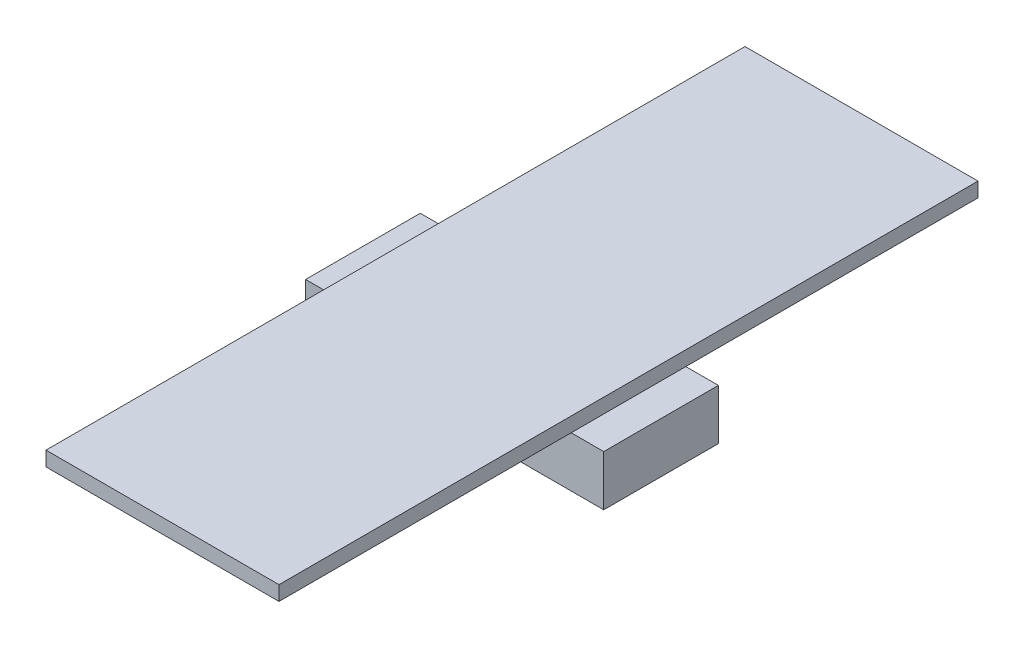
SolidWorks part; units mm, degrees
ref_plane "Front Plane" through (0, 0, 0) normal (0, 0, 1) x (1, 0, 0)
ref_plane "Top Plane" through (0, 0, 0) normal (0, 1, 0) x (1, 0, 0)
ref_plane "Right Plane" through (0, 0, 0) normal (1, 0, 0) x (0, 0, -1)
sketch "Sketch1" plane through (0, 0, 0) normal (0, 1, 0) x (1, 0, 0)
  line L1 (-65, -25) -> (65, -25)
  line L2 (-65, -25) -> (-65, 25)
  line L3 (-65, 25) -> (65, 25)
  line L4 (65, -25) -> (65, 25)
  line L5 (0, 25) -> (0, -25) construction
  line L6 (-65, 0) -> (65, 0) construction
  point P0 (0, 0)
  dimension "D1" = 130
  dimension "D2" = 50
extrude "Boss-Extrude1" add sketch "Sketch1" along normal blind 22
sketch "Sketch2" plane through (0, 0, 25) normal (0, 0, 1) x (1, 0, 0)
  ellipse E0 centre (0, 11) end of major axis (15.4617, 11) minor radius 5.8847
extrude "Cut-Extrude1" cut sketch "Sketch2" against normal through all
sketch "Sketch3" plane through (0, 22, 0) normal (0, 1, 0) x (1, 0, 0)
  line L1 (-50.8, -152.4) -> (50.8, -152.4)
  line L2 (-50.8, -152.4) -> (-50.8, 152.4)
  line L3 (-50.8, 152.4) -> (50.8, 152.4)
  line L4 (50.8, -152.4) -> (50.8, 152.4)
  line L5 (0, 152.4) -> (0, -152.4) construction
  line L6 (-50.8, 0) -> (50.8, 0) construction
  point P0 (0, 0)
  dimension "D1" = 101.6
  dimension "D2" = 304.8
extrude "Boss-Extrude2" add sketch "Sketch3" along normal blind 6.35
